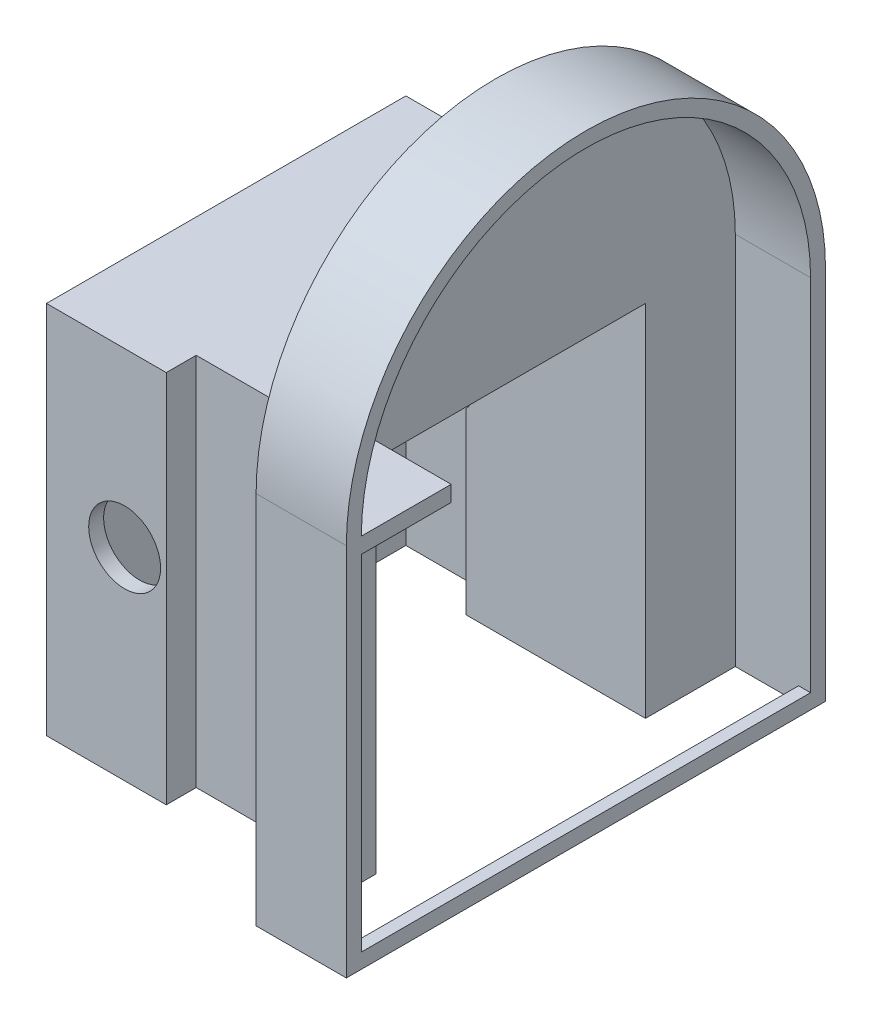
SolidWorks part; units mm, degrees
material "ABS"
ref_plane "Front Plane" through (0, 0, 0) normal (0, 0, 1) x (1, 0, 0)
ref_plane "Top Plane" through (0, 0, 0) normal (0, 1, 0) x (1, 0, 0)
ref_plane "Right Plane" through (0, 0, 0) normal (1, 0, 0) x (0, 0, -1)
sketch "Sketch1" plane through (0, 0, 0) normal (1, 0, 0) x (0, 0, -1)
  line L0 (-37.5232, 25.0235) -> (-37.5232, -99.9765)
  line L2 (117.4768, 25.0235) -> (117.4768, -94.9765)
  line L3 (117.4768, -94.9765) -> (-32.5232, -94.9765)
  line L4 (-32.5232, 25.0235) -> (-32.5232, -94.9765)
  line L5 (122.4768, -99.9765) -> (-37.5232, -99.9765)
  line L6 (122.4768, 25.0235) -> (122.4768, -99.9765)
  arc A0 (117.4768, 25.0235) -> (-32.5232, 25.0235) centre (42.4768, 25.0235) ccw
  arc A1 (122.4768, 25.0235) -> (-37.5232, 25.0235) centre (42.4768, 25.0235) ccw
  point P1 (-0.0232, 0.0235)
  dimension "D2" = 125
  dimension "D3" = 160
extrude "Boss-Extrude2" add sketch "Sketch1" along normal blind 150 contours A1 L0 L5 L6
sketch "Sketch4" plane through (0, 0, 37.5232) normal (0, 0, 1) x (1, 0, 0)
  line L1 (0, -99.9765) -> (40, -99.9765)
  line L2 (0, -99.9765) -> (0, 25.0235)
  line L3 (0, 25.0235) -> (40, 25.0235)
  line L4 (40, -99.9765) -> (40, 25.0235)
extrude "Cut-Extrude4" cut sketch "Sketch4" against normal blind 20
sketch "Sketch8" plane through (0, 0, 37.5232) normal (0, 0, 1) x (1, 0, 0)
  line L1 (40, -99.9765) -> (90, -99.9765)
  line L2 (40, -99.9765) -> (40, 25.0215)
  line L3 (40, 25.0215) -> (90, 25.0215)
  line L4 (90, -99.9765) -> (90, 25.0215)
extrude "Cut-Extrude8" cut sketch "Sketch8" against normal blind 30
sketch "Sketch9" plane through (0, 25.0235, 0) normal (0, -1, 0) x (1, 0, 0)
  line L0 (0, 37.5232) -> (0, 17.5232)
  line L1 (0, 17.5232) -> (40, 17.5232)
  line L2 (40, 17.5232) -> (40, 7.5232)
  line L3 (40, 7.5232) -> (90, 7.5232)
  line L4 (90, 7.5232) -> (90, 37.5232)
  line L5 (90, 37.5232) -> (0, 37.5232)
extrude "Cut-Extrude10" cut sketch "Sketch9" against normal through all both and the other way through all
sketch "Sketch11" plane through (0, 0, 7.5232) normal (0, 0, 1) x (1, 0, 0)
  line L1 (90, 25.0235) -> (-22.0222, 25.0235)
  line L2 (90, 25.0235) -> (90, 131.218)
  line L3 (90, 131.218) -> (-22.0222, 131.218)
  line L4 (-22.0222, 25.0235) -> (-22.0222, 131.218)
extrude "Cut-Extrude11" cut sketch "Sketch11" against normal through all both and the other way through all
sketch "Sketch12" plane through (150, 0, 0) normal (1, 0, 0) x (0, 0, -1)
  line L0 (-37.5232, 25.0235) -> (-37.5232, -99.9765)
  line L4 (122.4768, -99.9765) -> (-37.5232, -99.9765)
  line L5 (122.4768, 25.0235) -> (122.4768, -99.9765)
  line L7 (-32.5232, 25.0235) -> (-32.5232, -94.9765)
  line L8 (117.4768, -94.9765) -> (-32.5232, -94.9765)
  line L9 (117.4768, 25.0235) -> (117.4768, -94.9765)
  arc A1 (122.4768, 25.0235) -> (-37.5232, 25.0235) centre (42.4768, 25.0235) ccw
  arc A2 (117.4768, 25.0235) -> (-32.5232, 25.0235) centre (42.4768, 25.0235) ccw
  point P0 (-0.8105, 0.4525)
  dimension "D1" = 125
  dimension "D2" = 160
  dimension "D3" = 5
extrude "Cut-Extrude12" cut sketch "Sketch12" against normal blind 55 contours L9 A2 L7 L8 region at (150, -4.7409, -42.4768)
sketch "Sketch13" plane through (0, 0, -122.4768) normal (0, 0, -1) x (-1, 0, 0)
  line L0 (-40, -99.9765) -> (0, -99.9765)
  line L1 (-40, -99.9765) -> (-40, 25.0235)
  line L2 (-40, 25.0235) -> (0, 25.0235)
  line L3 (0, -99.9765) -> (0, 25.0235)
extrude "Cut-Extrude13" cut sketch "Sketch13" against normal blind 20
sketch "Sketch14" plane through (0, 0, -122.4768) normal (0, 0, -1) x (-1, 0, 0)
  line L0 (-90, -99.9765) -> (-40, -99.9765)
  line L1 (-90, -99.9765) -> (-90, 25.0235)
  line L2 (-90, 25.0235) -> (-40, 25.0235)
  line L3 (-40, -99.9765) -> (-40, 25.0235)
extrude "Cut-Extrude15" cut sketch "Sketch14" against normal blind 30
sketch "Sketch16" plane through (0, -99.9765, 0) normal (0, -1, 0) x (1, 0, 0)
  line L29 (95, -87.4768) -> (95, -117.4768)
  line L30 (95, -117.4768) -> (145, -117.4768)
  line L31 (145, -117.4768) -> (145, 32.5232)
  line L32 (145, 32.5232) -> (95, 32.5232)
  line L33 (95, 32.5232) -> (95, 2.5232)
  line L34 (95, 2.5232) -> (35, 2.5232)
  line L35 (35, 2.5232) -> (35, 12.5232)
  line L36 (35, 12.5232) -> (5, 12.5232)
  line L37 (5, 12.5232) -> (5, -97.4768)
  line L38 (5, -97.4768) -> (35, -97.4768)
  line L39 (35, -97.4768) -> (35, -87.4768)
  line L40 (35, -87.4768) -> (95, -87.4768)
  line L41 (95, -87.4768) -> (95, -117.4768)
  line L42 (95, -117.4768) -> (145, -117.4768)
  line L43 (145, -117.4768) -> (145, 32.5232)
  line L44 (145, 32.5232) -> (95, 32.5232)
  line L45 (95, 32.5232) -> (95, 2.5232)
  line L46 (95, 2.5232) -> (35, 2.5232)
  line L47 (35, 2.5232) -> (35, 12.5232)
  line L48 (35, 12.5232) -> (5, 12.5232)
  line L49 (5, 12.5232) -> (5, -97.4768)
  line L50 (5, -97.4768) -> (35, -97.4768)
  line L51 (35, -97.4768) -> (35, -87.4768)
  line L52 (35, -87.4768) -> (95, -87.4768)
  dimension "D1" = 5
extrude "Cut-Extrude17" cut sketch "Sketch16" against normal blind 120
sketch "Sketch17" plane through (95, 0, 0) normal (1, 0, 0) x (0, 0, -1)
  line L0 (-32.5232, 25.0235) -> (-32.5232, -94.9765) construction
  line L1 (-2.5232, 20.0235) -> (-32.5232, 20.0235)
  line L2 (-2.5232, 20.0235) -> (-2.5232, 25.283)
  line L3 (-2.5232, 25.283) -> (-32.5232, 25.283)
  line L4 (-32.5232, 20.0235) -> (-32.5232, 25.283)
extrude "Boss-Extrude3" add sketch "Sketch17" along normal blind 55
sketch "Sketch20" plane through (0, 0, 7.5232) normal (0, 0, 1) x (1, 0, 0)
  circle A3 centre (26.0978, -32.4506) radius 12
extrude "Cut-Extrude18" cut sketch "Sketch20" against normal through all both and the other way through all
sketch "Sketch21" plane through (0, 0, -122.4768) normal (0, 0, -1) x (-1, 0, 0)
  line L1 (-120.1273, -103.0146) -> (-120.1273, 116.236)
extrude "Cut-Extrude-Thin2" cut sketch "Sketch21" against normal through all both and the other way through all thin thin type one direction reverse wall 50
sketch "Sketch22" plane through (0, -99.9765, 0) normal (0, -1, 0) x (1, 0, 0)
  line L1 (120.1273, 37.5232) -> (116.1273, 37.5232)
  line L2 (120.1273, 37.5232) -> (120.1273, -122.4768)
  line L3 (120.1273, -122.4768) -> (116.1273, -122.4768)
  line L4 (116.1273, 37.5232) -> (116.1273, -122.4768)
extrude "Boss-Extrude4" add sketch "Sketch22" against normal blind 5
sketch "Sketch25" plane through (0, 0, 0) normal (-1, 0, 0) x (0, 0, 1)
  line L0 (-30.1902, -63.4375) -> (-30.1902, -11.8375)
  line L1 (-54.1902, -63.4375) -> (-30.1902, -63.4375)
  line L2 (-54.1902, -11.8375) -> (-54.1902, -63.4375)
  line L3 (-30.1902, -11.8375) -> (-54.1902, -11.8375)
  line L4 (-57.1902, -66.4375) -> (-27.1902, -66.4375)
  line L5 (-27.1902, -66.4375) -> (-27.1902, -8.8375)
  line L6 (-27.1902, -8.8375) -> (-57.1902, -8.8375)
  line L7 (-57.1902, -8.8375) -> (-57.1902, -66.4375)
  dimension "D1" = 3
extrude "Boss-Extrude5" add sketch "Sketch25" against normal blind 18 contours L7 L4 L5 L6
extrude "Cut-Extrude19" cut sketch "Sketch25<4>" against normal blind 13 contours L0 L3 L2 L1 region at (0, -37.6375, -42.1902)
sketch "Sketch25<4>" plane through (0, 0, 0) normal (-1, 0, 0) x (0, 0, 1) same geometry as "Sketch25"
sketch "Sketch26" plane through (0, -63.4375, 0) normal (0, 1, 0) x (1, 0, 0)
  line L1 (0.3, 36.5945) -> (0.9878, 36.5945)
  line L2 (0.3, 36.5945) -> (0.3, 31.3263)
  line L3 (0.3, 31.3263) -> (0.9878, 31.3263)
  line L4 (0.9878, 36.5945) -> (0.9878, 31.3263)
  line L5 (0.3, 52.0253) -> (0.9878, 52.0253)
  line L6 (0.3, 52.0253) -> (0.3, 54.2445)
  line L7 (0.3, 54.2445) -> (0.9878, 54.2445)
  line L8 (0.9878, 52.0253) -> (0.9878, 54.2445)
  line L10 (0, 54.1902) -> (0, 30.1902) construction
  dimension "D1" = 0.3
  dimension "D2" = 1.1361
  dimension "D3" = 17.6499
  dimension "D4" = 2.1649
extrude "Cut-Extrude21" cut sketch "Sketch26" against normal blind 1
sketch "Sketch28" plane through (0, -8.8375, 0) normal (0, 1, 0) x (1, 0, 0)
  circle A0 centre (10.1491, 44.5402) radius 0.75
  circle A1 centre (10.1491, 39.8402) radius 0.75
extrude "Cut-Extrude22" cut sketch "Sketch28" against normal blind 5 and the other way blind 5 contours A0 | A1 region at (10.1491, -8.8375, -44.5402) region at (10.1491, -8.8375, -39.8402)
